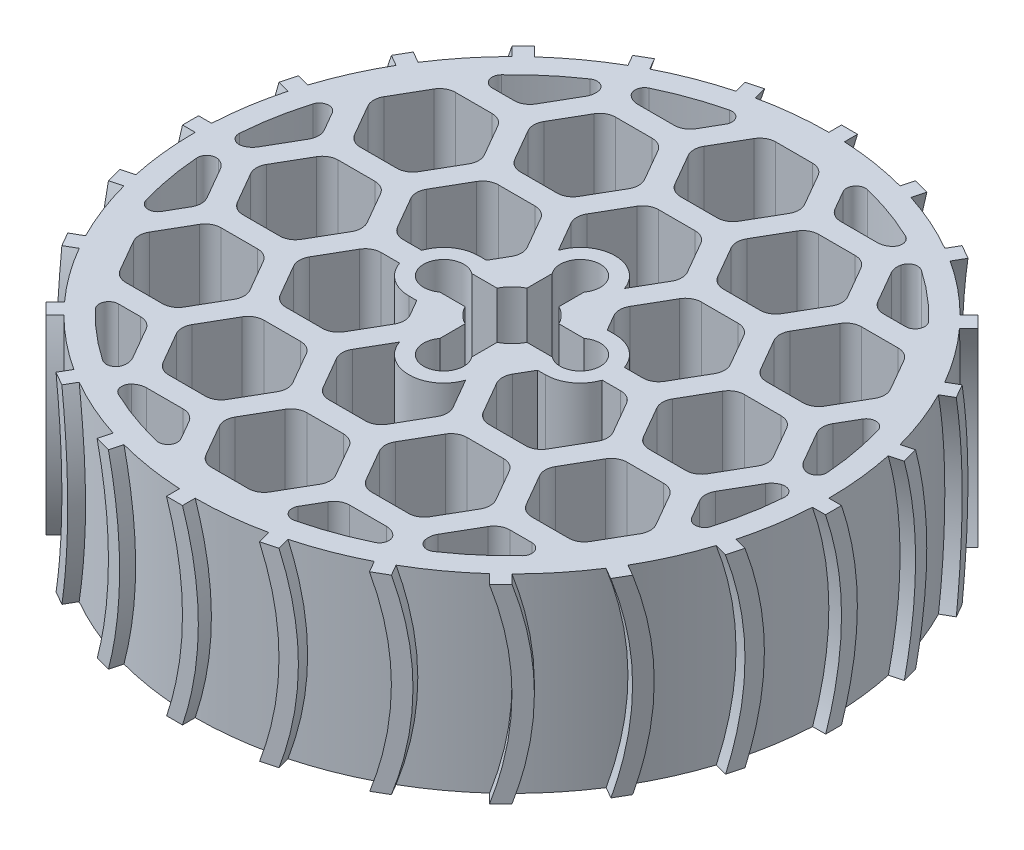
SolidWorks part; units mm, degrees
ref_plane "Front Plane" through (0, 0, 0) normal (0, 0, 1) x (1, 0, 0)
ref_plane "Top Plane" through (0, 0, 0) normal (0, 1, 0) x (1, 0, 0)
ref_plane "Right Plane" through (0, 0, 0) normal (1, 0, 0) x (0, 0, -1)
sketch "Sketch2" plane through (0, 0, 0) normal (0, 1, 0) x (1, 0, 0)
  line L0 (-17.7275, -5.0583) -> (-9.768, -5.0583)
  line L1 (-17.7275, 5.0583) -> (-9.768, 5.0583)
  line L2 (-21.548, 11) -> (-11, 11)
  line L3 (-21.548, -11) -> (-11, -11)
  line L4 (-21.548, 0) -> (0, 0) construction
  line L5 (11, 21.548) -> (11, 11)
  line L6 (-11, 21.548) -> (-11, 11)
  line L7 (5.0583, 17.7275) -> (5.0583, 9.768)
  line L8 (-5.0583, 17.7275) -> (-5.0583, 9.768)
  line L9 (21.548, -11) -> (11, -11)
  line L10 (21.548, 11) -> (11, 11)
  line L11 (17.7275, -5.0583) -> (9.768, -5.0583)
  line L12 (17.7275, 5.0583) -> (9.768, 5.0583)
  line L13 (-11, -21.548) -> (-11, -11)
  line L14 (11, -21.548) -> (11, -11)
  line L15 (-5.0583, -17.7275) -> (-5.0583, -9.768)
  line L16 (5.0583, -17.7275) -> (5.0583, -9.768)
  line L17 (0, 0) -> (-12.9904, 7.5) construction
  line L18 (-15.8771, -2.5) -> (-10.1036, -12.5)
  line L19 (-5.7735, -15) -> (5.7735, -15)
  line L20 (10.1036, -12.5) -> (15.8771, -2.5)
  line L21 (15.8771, 2.5) -> (10.1036, 12.5)
  line L22 (5.7735, 15) -> (-5.7735, 15)
  line L23 (-10.1036, 12.5) -> (-15.8771, 2.5)
  arc A0 (-21.548, 11) -> (-21.548, -11) centre (-21.548, 0) ccw
  arc A1 (-5.0583, 9.768) -> (-9.768, 5.0583) centre (0, 0) ccw
  circle A2 centre (-21.548, 0) radius 3.302
  circle A3 centre (-21.548, 0) radius 6.339
  arc A4 (-5.0583, 9.768) -> (-9.768, 5.0583) centre (0, 0) ccw
  arc A5 (11, 21.548) -> (-11, 21.548) centre (0, 21.548) ccw
  circle A6 centre (0, 21.548) radius 6.339
  circle A7 centre (0, 21.548) radius 3.302
  arc A8 (21.548, -11) -> (21.548, 11) centre (21.548, 0) ccw
  circle A9 centre (21.548, 0) radius 6.339
  circle A10 centre (21.548, 0) radius 3.302
  arc A11 (-11, -21.548) -> (11, -21.548) centre (0, -21.548) ccw
  circle A12 centre (0, -21.548) radius 6.339
  circle A13 centre (0, -21.548) radius 3.302
  arc A14 (9.768, 5.0583) -> (5.0583, 9.768) centre (0, 0) ccw
  arc A15 (5.0583, -9.768) -> (9.768, -5.0583) centre (0, 0) ccw
  arc A16 (-9.768, -5.0583) -> (-5.0583, -9.768) centre (0, 0) ccw
  circle A17 centre (0, 0) radius 100
  circle A18 centre (0, 0) radius 15 construction
  arc A19 (10.1036, 12.5) -> (5.7735, 15) centre (5.7735, 10) ccw
  arc A20 (15.8771, -2.5) -> (15.8771, 2.5) centre (11.547, 0) ccw
  arc A21 (10.1036, -12.5) -> (5.7735, -15) centre (5.7735, -10) cw
  arc A22 (-10.1036, -12.5) -> (-5.7735, -15) centre (-5.7735, -10) ccw
  arc A23 (-15.8771, -2.5) -> (-15.8771, 2.5) centre (-11.547, 0) cw
  arc A24 (-10.1036, 12.5) -> (-5.7735, 15) centre (-5.7735, 10) cw
  point P59 (0, 0)
  dimension "D1" = 6.604
  dimension "D2" = 12.678
  dimension "D3" = 11
  dimension "D8" = 22
  dimension "D10" = 200
  dimension "D12" = 5
  dimension "D4" = 21.548
  dimension "D5" = 7.9595
  dimension "D6" = 10.548
  dimension "D7" = 10.548
  dimension "D11" = 30
  dimension "D13" = 30
  dimension "D9" = 4
sketch "Sketch3" plane through (0, 0, 0) normal (0, 1, 0) x (1, 0, 0)
  line L0 (0, 0) -> (16.547, 0) construction
  line L1 (5.7735, 15) -> (-5.7735, 15)
  line L2 (-10.1036, 12.5) -> (-15.8771, 2.5)
  line L3 (-15.8771, -2.5) -> (-10.1036, -12.5)
  line L4 (-5.7735, -15) -> (5.7735, -15)
  line L5 (10.1036, -12.5) -> (15.8771, -2.5)
  line L6 (15.8771, 2.5) -> (10.1036, 12.5)
  line L7 (37.8164, 33.5) -> (26.2694, 33.5)
  line L8 (21.9393, 31) -> (16.1658, 21)
  line L9 (16.1658, 16) -> (21.9393, 6)
  line L10 (26.2694, 3.5) -> (37.8164, 3.5)
  line L11 (42.1466, 6) -> (47.9201, 16)
  line L12 (47.9201, 21) -> (42.1466, 31)
  line L13 (69.8594, 52) -> (58.3124, 52)
  line L14 (53.9823, 49.5) -> (48.2087, 39.5)
  line L15 (48.2087, 34.5) -> (53.9823, 24.5)
  line L16 (58.3124, 22) -> (69.8594, 22)
  line L17 (74.1895, 24.5) -> (79.963, 34.5)
  line L18 (79.963, 39.5) -> (74.1895, 49.5)
  line L19 (101.9023, 70.5) -> (90.3553, 70.5)
  line L20 (86.0252, 68) -> (80.2517, 58)
  line L21 (80.2517, 53) -> (86.0252, 43)
  line L22 (90.3553, 40.5) -> (101.9023, 40.5)
  line L23 (106.2324, 43) -> (112.006, 53)
  line L24 (112.006, 58) -> (106.2324, 68)
  line L25 (37.8164, 70.5) -> (26.2694, 70.5)
  line L26 (21.9393, 68) -> (16.1658, 58)
  line L27 (16.1658, 53) -> (21.9393, 43)
  line L28 (26.2694, 40.5) -> (37.8164, 40.5)
  line L29 (42.1466, 43) -> (47.9201, 53)
  line L30 (47.9201, 58) -> (42.1466, 68)
  line L31 (69.8594, 89) -> (58.3124, 89)
  line L32 (53.9823, 86.5) -> (48.2087, 76.5)
  line L33 (48.2087, 71.5) -> (53.9823, 61.5)
  line L34 (58.3124, 59) -> (69.8594, 59)
  line L35 (74.1895, 61.5) -> (79.963, 71.5)
  line L36 (79.963, 76.5) -> (74.1895, 86.5)
  line L37 (101.9023, 107.5) -> (90.3553, 107.5) [skipped]
  line L38 (86.0252, 105) -> (80.2517, 95) [skipped]
  line L39 (80.2517, 90) -> (86.0252, 80) [skipped]
  line L40 (90.3553, 77.5) -> (101.9023, 77.5) [skipped]
  line L41 (106.2324, 80) -> (112.006, 90) [skipped]
  line L42 (112.006, 95) -> (106.2324, 105) [skipped]
  line L43 (37.8164, 107.5) -> (26.2694, 107.5)
  line L44 (21.9393, 105) -> (16.1658, 95)
  line L45 (16.1658, 90) -> (21.9393, 80)
  line L46 (26.2694, 77.5) -> (37.8164, 77.5)
  line L47 (42.1466, 80) -> (47.9201, 90)
  line L48 (47.9201, 95) -> (42.1466, 105)
  line L49 (69.8594, 126) -> (58.3124, 126) [skipped]
  line L50 (53.9823, 123.5) -> (48.2087, 113.5) [skipped]
  line L51 (48.2087, 108.5) -> (53.9823, 98.5) [skipped]
  line L52 (58.3124, 96) -> (69.8594, 96) [skipped]
  line L53 (74.1895, 98.5) -> (79.963, 108.5) [skipped]
  line L54 (79.963, 113.5) -> (74.1895, 123.5) [skipped]
  line L55 (101.9023, 144.5) -> (90.3553, 144.5) [skipped]
  line L56 (86.0252, 142) -> (80.2517, 132) [skipped]
  line L57 (80.2517, 127) -> (86.0252, 117) [skipped]
  line L58 (90.3553, 114.5) -> (101.9023, 114.5) [skipped]
  line L59 (106.2324, 117) -> (112.006, 127) [skipped]
  line L60 (112.006, 132) -> (106.2324, 142) [skipped]
  line L61 (37.8164, 144.5) -> (26.2694, 144.5) [skipped]
  line L62 (21.9393, 142) -> (16.1658, 132) [skipped]
  line L63 (16.1658, 127) -> (21.9393, 117) [skipped]
  line L64 (26.2694, 114.5) -> (37.8164, 114.5) [skipped]
  line L65 (42.1466, 117) -> (47.9201, 127) [skipped]
  line L66 (47.9201, 132) -> (42.1466, 142) [skipped]
  line L67 (69.8594, 163) -> (58.3124, 163) [skipped]
  line L68 (53.9823, 160.5) -> (48.2087, 150.5) [skipped]
  line L69 (48.2087, 145.5) -> (53.9823, 135.5) [skipped]
  line L70 (58.3124, 133) -> (69.8594, 133) [skipped]
  line L71 (74.1895, 135.5) -> (79.963, 145.5) [skipped]
  line L72 (79.963, 150.5) -> (74.1895, 160.5) [skipped]
  line L73 (101.9023, 181.5) -> (90.3553, 181.5) [skipped]
  line L74 (86.0252, 179) -> (80.2517, 169) [skipped]
  line L75 (80.2517, 164) -> (86.0252, 154) [skipped]
  line L76 (90.3553, 151.5) -> (101.9023, 151.5) [skipped]
  line L77 (106.2324, 154) -> (112.006, 164) [skipped]
  line L78 (112.006, 169) -> (106.2324, 179) [skipped]
  line L79 (5.7735, 52) -> (-5.7735, 52) [skipped]
  line L80 (-10.1036, 49.5) -> (-15.8771, 39.5) [skipped]
  line L81 (-15.8771, 34.5) -> (-10.1036, 24.5) [skipped]
  line L82 (-5.7735, 22) -> (5.7735, 22) [skipped]
  line L83 (10.1036, 24.5) -> (15.8771, 34.5) [skipped]
  line L84 (15.8771, 39.5) -> (10.1036, 49.5) [skipped]
  line L85 (5.7735, 89) -> (-5.7735, 89) [skipped]
  line L86 (-10.1036, 86.5) -> (-15.8771, 76.5) [skipped]
  line L87 (-15.8771, 71.5) -> (-10.1036, 61.5) [skipped]
  line L88 (-5.7735, 59) -> (5.7735, 59) [skipped]
  line L89 (10.1036, 61.5) -> (15.8771, 71.5) [skipped]
  line L90 (15.8771, 76.5) -> (10.1036, 86.5) [skipped]
  line L91 (5.7735, 126) -> (-5.7735, 126) [skipped]
  line L92 (-10.1036, 123.5) -> (-15.8771, 113.5) [skipped]
  line L93 (-15.8771, 108.5) -> (-10.1036, 98.5) [skipped]
  line L94 (-5.7735, 96) -> (5.7735, 96) [skipped]
  line L95 (10.1036, 98.5) -> (15.8771, 108.5) [skipped]
  line L96 (15.8771, 113.5) -> (10.1036, 123.5) [skipped]
  line L97 (0, 0) -> (83.1384, 48) construction
  line L98 (112.006, 21) -> (106.2324, 31)
  line L99 (101.9023, 33.5) -> (90.3553, 33.5)
  line L100 (86.0252, 31) -> (80.2517, 21)
  line L101 (80.2517, 16) -> (86.0252, 6)
  line L102 (90.3553, 3.5) -> (101.9023, 3.5)
  line L103 (106.2324, 6) -> (112.006, 16)
  line L104 (112.006, -16) -> (106.2324, -6)
  line L105 (101.9023, -3.5) -> (90.3553, -3.5)
  line L106 (86.0252, -6) -> (80.2517, -16)
  line L107 (80.2517, -21) -> (86.0252, -31)
  line L108 (90.3553, -33.5) -> (101.9023, -33.5)
  line L109 (106.2324, -31) -> (112.006, -21)
  line L110 (112.006, -53) -> (106.2324, -43)
  line L111 (101.9023, -40.5) -> (90.3553, -40.5)
  line L112 (86.0252, -43) -> (80.2517, -53)
  line L113 (80.2517, -58) -> (86.0252, -68)
  line L114 (90.3553, -70.5) -> (101.9023, -70.5)
  line L115 (106.2324, -68) -> (112.006, -58)
  line L116 (79.963, -34.5) -> (74.1895, -24.5)
  line L117 (69.8594, -22) -> (58.3124, -22)
  line L118 (53.9823, -24.5) -> (48.2087, -34.5)
  line L119 (48.2087, -39.5) -> (53.9823, -49.5)
  line L120 (58.3124, -52) -> (69.8594, -52)
  line L121 (74.1895, -49.5) -> (79.963, -39.5)
  line L122 (79.963, 2.5) -> (74.1895, 12.5)
  line L123 (69.8594, 15) -> (58.3124, 15)
  line L124 (53.9823, 12.5) -> (48.2087, 2.5)
  line L125 (48.2087, -2.5) -> (53.9823, -12.5)
  line L126 (58.3124, -15) -> (69.8594, -15)
  line L127 (74.1895, -12.5) -> (79.963, -2.5)
  line L128 (47.9201, -16) -> (42.1466, -6)
  line L129 (37.8164, -3.5) -> (26.2694, -3.5)
  line L130 (21.9393, -6) -> (16.1658, -16)
  line L131 (16.1658, -21) -> (21.9393, -31)
  line L132 (26.2694, -33.5) -> (37.8164, -33.5)
  line L133 (42.1466, -31) -> (47.9201, -21)
  line L134 (74.1895, -86.5) -> (79.963, -76.5)
  line L135 (79.963, -71.5) -> (74.1895, -61.5)
  line L136 (69.8594, -59) -> (58.3124, -59)
  line L137 (53.9823, -61.5) -> (48.2087, -71.5)
  line L138 (48.2087, -76.5) -> (53.9823, -86.5)
  line L139 (58.3124, -89) -> (69.8594, -89)
  line L140 (42.1466, -105) -> (47.9201, -95)
  line L141 (47.9201, -90) -> (42.1466, -80)
  line L142 (37.8164, -77.5) -> (26.2694, -77.5)
  line L143 (21.9393, -80) -> (16.1658, -90)
  line L144 (16.1658, -95) -> (21.9393, -105)
  line L145 (26.2694, -107.5) -> (37.8164, -107.5)
  line L146 (10.1036, -123.5) -> (15.8771, -113.5)
  line L147 (15.8771, -108.5) -> (10.1036, -98.5)
  line L148 (5.7735, -96) -> (-5.7735, -96)
  line L149 (-10.1036, -98.5) -> (-15.8771, -108.5)
  line L150 (-15.8771, -113.5) -> (-10.1036, -123.5)
  line L151 (-5.7735, -126) -> (5.7735, -126)
  line L152 (10.1036, -86.5) -> (15.8771, -76.5)
  line L153 (15.8771, -71.5) -> (10.1036, -61.5)
  line L154 (5.7735, -59) -> (-5.7735, -59)
  line L155 (-10.1036, -61.5) -> (-15.8771, -71.5)
  line L156 (-15.8771, -76.5) -> (-10.1036, -86.5)
  line L157 (-5.7735, -89) -> (5.7735, -89)
  line L158 (42.1466, -68) -> (47.9201, -58)
  line L159 (47.9201, -53) -> (42.1466, -43)
  line L160 (37.8164, -40.5) -> (26.2694, -40.5)
  line L161 (21.9393, -43) -> (16.1658, -53)
  line L162 (16.1658, -58) -> (21.9393, -68)
  line L163 (26.2694, -70.5) -> (37.8164, -70.5)
  line L164 (10.1036, -49.5) -> (15.8771, -39.5)
  line L165 (15.8771, -34.5) -> (10.1036, -24.5)
  line L166 (5.7735, -22) -> (-5.7735, -22)
  line L167 (-10.1036, -24.5) -> (-15.8771, -34.5)
  line L168 (-15.8771, -39.5) -> (-10.1036, -49.5)
  line L169 (-5.7735, -52) -> (5.7735, -52)
  line L170 (-37.8164, -107.5) -> (-26.2694, -107.5)
  line L171 (-21.9393, -105) -> (-16.1658, -95)
  line L172 (-16.1658, -90) -> (-21.9393, -80)
  line L173 (-26.2694, -77.5) -> (-37.8164, -77.5)
  line L174 (-42.1466, -80) -> (-47.9201, -90)
  line L175 (-47.9201, -95) -> (-42.1466, -105)
  line L176 (-69.8594, -89) -> (-58.3124, -89)
  line L177 (-53.9823, -86.5) -> (-48.2087, -76.5)
  line L178 (-48.2087, -71.5) -> (-53.9823, -61.5)
  line L179 (-58.3124, -59) -> (-69.8594, -59)
  line L180 (-74.1895, -61.5) -> (-79.963, -71.5)
  line L181 (-79.963, -76.5) -> (-74.1895, -86.5)
  line L182 (-101.9023, -70.5) -> (-90.3553, -70.5)
  line L183 (-86.0252, -68) -> (-80.2517, -58)
  line L184 (-80.2517, -53) -> (-86.0252, -43)
  line L185 (-90.3553, -40.5) -> (-101.9023, -40.5)
  line L186 (-106.2324, -43) -> (-112.006, -53)
  line L187 (-112.006, -58) -> (-106.2324, -68)
  line L188 (-69.8594, -52) -> (-58.3124, -52)
  line L189 (-53.9823, -49.5) -> (-48.2087, -39.5)
  line L190 (-48.2087, -34.5) -> (-53.9823, -24.5)
  line L191 (-58.3124, -22) -> (-69.8594, -22)
  line L192 (-74.1895, -24.5) -> (-79.963, -34.5)
  line L193 (-79.963, -39.5) -> (-74.1895, -49.5)
  line L194 (-37.8164, -70.5) -> (-26.2694, -70.5)
  line L195 (-21.9393, -68) -> (-16.1658, -58)
  line L196 (-16.1658, -53) -> (-21.9393, -43)
  line L197 (-26.2694, -40.5) -> (-37.8164, -40.5)
  line L198 (-42.1466, -43) -> (-47.9201, -53)
  line L199 (-47.9201, -58) -> (-42.1466, -68)
  line L200 (-37.8164, -33.5) -> (-26.2694, -33.5)
  line L201 (-21.9393, -31) -> (-16.1658, -21)
  line L202 (-16.1658, -16) -> (-21.9393, -6)
  line L203 (-26.2694, -3.5) -> (-37.8164, -3.5)
  line L204 (-42.1466, -6) -> (-47.9201, -16)
  line L205 (-47.9201, -21) -> (-42.1466, -31)
  line L206 (-112.006, -21) -> (-106.2324, -31)
  line L207 (-101.9023, -33.5) -> (-90.3553, -33.5)
  line L208 (-86.0252, -31) -> (-80.2517, -21)
  line L209 (-80.2517, -16) -> (-86.0252, -6)
  line L210 (-90.3553, -3.5) -> (-101.9023, -3.5)
  line L211 (-106.2324, -6) -> (-112.006, -16)
  line L212 (-112.006, 16) -> (-106.2324, 6)
  line L213 (-101.9023, 3.5) -> (-90.3553, 3.5)
  line L214 (-86.0252, 6) -> (-80.2517, 16)
  line L215 (-80.2517, 21) -> (-86.0252, 31)
  line L216 (-90.3553, 33.5) -> (-101.9023, 33.5)
  line L217 (-106.2324, 31) -> (-112.006, 21)
  line L218 (-112.006, 53) -> (-106.2324, 43)
  line L219 (-101.9023, 40.5) -> (-90.3553, 40.5)
  line L220 (-86.0252, 43) -> (-80.2517, 53)
  line L221 (-80.2517, 58) -> (-86.0252, 68)
  line L222 (-90.3553, 70.5) -> (-101.9023, 70.5)
  line L223 (-106.2324, 68) -> (-112.006, 58)
  line L224 (-79.963, 34.5) -> (-74.1895, 24.5)
  line L225 (-69.8594, 22) -> (-58.3124, 22)
  line L226 (-53.9823, 24.5) -> (-48.2087, 34.5)
  line L227 (-48.2087, 39.5) -> (-53.9823, 49.5)
  line L228 (-58.3124, 52) -> (-69.8594, 52)
  line L229 (-74.1895, 49.5) -> (-79.963, 39.5)
  line L230 (-79.963, -2.5) -> (-74.1895, -12.5)
  line L231 (-69.8594, -15) -> (-58.3124, -15)
  line L232 (-53.9823, -12.5) -> (-48.2087, -2.5)
  line L233 (-48.2087, 2.5) -> (-53.9823, 12.5)
  line L234 (-58.3124, 15) -> (-69.8594, 15)
  line L235 (-74.1895, 12.5) -> (-79.963, 2.5)
  line L236 (-47.9201, 16) -> (-42.1466, 6)
  line L237 (-37.8164, 3.5) -> (-26.2694, 3.5)
  line L238 (-21.9393, 6) -> (-16.1658, 16)
  line L239 (-16.1658, 21) -> (-21.9393, 31)
  line L240 (-26.2694, 33.5) -> (-37.8164, 33.5)
  line L241 (-42.1466, 31) -> (-47.9201, 21)
  line L242 (-74.1895, 86.5) -> (-79.963, 76.5)
  line L243 (-79.963, 71.5) -> (-74.1895, 61.5)
  line L244 (-69.8594, 59) -> (-58.3124, 59)
  line L245 (-53.9823, 61.5) -> (-48.2087, 71.5)
  line L246 (-48.2087, 76.5) -> (-53.9823, 86.5)
  line L247 (-58.3124, 89) -> (-69.8594, 89)
  line L248 (-42.1466, 105) -> (-47.9201, 95)
  line L249 (-47.9201, 90) -> (-42.1466, 80)
  line L250 (-37.8164, 77.5) -> (-26.2694, 77.5)
  line L251 (-21.9393, 80) -> (-16.1658, 90)
  line L252 (-16.1658, 95) -> (-21.9393, 105)
  line L253 (-26.2694, 107.5) -> (-37.8164, 107.5)
  line L254 (-10.1036, 123.5) -> (-15.8771, 113.5)
  line L255 (-15.8771, 108.5) -> (-10.1036, 98.5)
  line L256 (-5.7735, 96) -> (5.7735, 96)
  line L257 (10.1036, 98.5) -> (15.8771, 108.5)
  line L258 (15.8771, 113.5) -> (10.1036, 123.5)
  line L259 (5.7735, 126) -> (-5.7735, 126)
  line L260 (-10.1036, 86.5) -> (-15.8771, 76.5)
  line L261 (-15.8771, 71.5) -> (-10.1036, 61.5)
  line L262 (-5.7735, 59) -> (5.7735, 59)
  line L263 (10.1036, 61.5) -> (15.8771, 71.5)
  line L264 (15.8771, 76.5) -> (10.1036, 86.5)
  line L265 (5.7735, 89) -> (-5.7735, 89)
  line L266 (-42.1466, 68) -> (-47.9201, 58)
  line L267 (-47.9201, 53) -> (-42.1466, 43)
  line L268 (-37.8164, 40.5) -> (-26.2694, 40.5)
  line L269 (-21.9393, 43) -> (-16.1658, 53)
  line L270 (-16.1658, 58) -> (-21.9393, 68)
  line L271 (-26.2694, 70.5) -> (-37.8164, 70.5)
  line L272 (-10.1036, 49.5) -> (-15.8771, 39.5)
  line L273 (-15.8771, 34.5) -> (-10.1036, 24.5)
  line L274 (-5.7735, 22) -> (5.7735, 22)
  line L275 (10.1036, 24.5) -> (15.8771, 34.5)
  line L276 (15.8771, 39.5) -> (10.1036, 49.5)
  line L277 (5.7735, 52) -> (-5.7735, 52)
  line L278 (0, 0) -> (0, 96) construction
  line L279 (0, 0) -> (-83.1384, 48) construction
  line L280 (-17.7275, -5.0583) -> (-9.768, -5.0583)
  line L281 (-17.7275, 5.0583) -> (-9.768, 5.0583)
  line L282 (-21.548, 11) -> (-11, 11)
  line L283 (-21.548, -11) -> (-11, -11)
  line L284 (0, 0) -> (-21.548, 0) construction
  line L285 (11, 21.548) -> (11, 11)
  line L286 (-11, 21.548) -> (-11, 11)
  line L287 (-5.0583, 17.7275) -> (-5.0583, 9.768)
  line L288 (5.0583, 17.7275) -> (5.0583, 9.768)
  line L289 (21.548, -11) -> (11, -11)
  line L290 (21.548, 11) -> (11, 11)
  line L291 (17.7275, 5.0583) -> (9.768, 5.0583)
  line L292 (17.7275, -5.0583) -> (9.768, -5.0583)
  line L293 (-11, -21.548) -> (-11, -11)
  line L294 (11, -21.548) -> (11, -11)
  line L295 (5.0583, -17.7275) -> (5.0583, -9.768)
  line L296 (-5.0583, -17.7275) -> (-5.0583, -9.768)
  line L297 (0, 0) -> (0, 21.548) construction
  circle A0 centre (0, 0) radius 15 construction
  arc A1 (10.1036, 12.5) -> (5.7735, 15) centre (5.7735, 10) ccw
  arc A2 (15.8771, 2.5) -> (15.8771, -2.5) centre (11.547, 0) cw
  arc A3 (5.7735, -15) -> (10.1036, -12.5) centre (5.7735, -10) ccw
  arc A4 (-5.7735, -15) -> (-10.1036, -12.5) centre (-5.7735, -10) cw
  arc A5 (-15.8771, -2.5) -> (-15.8771, 2.5) centre (-11.547, 0) cw
  arc A6 (-10.1036, 12.5) -> (-5.7735, 15) centre (-5.7735, 10) cw
  circle A7 centre (0, 0) radius 100
  arc A8 (21.9393, 31) -> (26.2694, 33.5) centre (26.2694, 28.5) cw
  arc A9 (42.1466, 31) -> (37.8164, 33.5) centre (37.8164, 28.5) ccw
  arc A10 (16.1658, 16) -> (16.1658, 21) centre (20.4959, 18.5) cw
  arc A11 (26.2694, 3.5) -> (21.9393, 6) centre (26.2694, 8.5) cw
  arc A12 (37.8164, 3.5) -> (42.1466, 6) centre (37.8164, 8.5) ccw
  arc A13 (47.9201, 21) -> (47.9201, 16) centre (43.5899, 18.5) cw
  arc A14 (53.9823, 49.5) -> (58.3124, 52) centre (58.3124, 47) cw
  arc A15 (74.1895, 49.5) -> (69.8594, 52) centre (69.8594, 47) ccw
  arc A16 (48.2087, 34.5) -> (48.2087, 39.5) centre (52.5389, 37) cw
  arc A17 (58.3124, 22) -> (53.9823, 24.5) centre (58.3124, 27) cw
  arc A18 (69.8594, 22) -> (74.1895, 24.5) centre (69.8594, 27) ccw
  arc A19 (79.963, 39.5) -> (79.963, 34.5) centre (75.6329, 37) cw
  arc A20 (86.0252, 68) -> (90.3553, 70.5) centre (90.3553, 65.5) cw
  arc A21 (106.2324, 68) -> (101.9023, 70.5) centre (101.9023, 65.5) ccw
  arc A22 (80.2517, 53) -> (80.2517, 58) centre (84.5818, 55.5) cw
  arc A23 (90.3553, 40.5) -> (86.0252, 43) centre (90.3553, 45.5) cw
  arc A24 (101.9023, 40.5) -> (106.2324, 43) centre (101.9023, 45.5) ccw
  arc A25 (112.006, 58) -> (112.006, 53) centre (107.6758, 55.5) cw
  arc A26 (21.9393, 68) -> (26.2694, 70.5) centre (26.2694, 65.5) cw
  arc A27 (42.1466, 68) -> (37.8164, 70.5) centre (37.8164, 65.5) ccw
  arc A28 (16.1658, 53) -> (16.1658, 58) centre (20.4959, 55.5) cw
  arc A29 (26.2694, 40.5) -> (21.9393, 43) centre (26.2694, 45.5) cw
  arc A30 (37.8164, 40.5) -> (42.1466, 43) centre (37.8164, 45.5) ccw
  arc A31 (47.9201, 58) -> (47.9201, 53) centre (43.5899, 55.5) cw
  arc A32 (53.9823, 86.5) -> (58.3124, 89) centre (58.3124, 84) cw
  arc A33 (74.1895, 86.5) -> (69.8594, 89) centre (69.8594, 84) ccw
  arc A34 (48.2087, 71.5) -> (48.2087, 76.5) centre (52.5389, 74) cw
  arc A35 (58.3124, 59) -> (53.9823, 61.5) centre (58.3124, 64) cw
  arc A36 (69.8594, 59) -> (74.1895, 61.5) centre (69.8594, 64) ccw
  arc A37 (79.963, 76.5) -> (79.963, 71.5) centre (75.6329, 74) cw
  arc A38 (86.0252, 105) -> (90.3553, 107.5) centre (90.3553, 102.5) cw [skipped]
  arc A39 (106.2324, 105) -> (101.9023, 107.5) centre (101.9023, 102.5) ccw [skipped]
  arc A40 (80.2517, 90) -> (80.2517, 95) centre (84.5818, 92.5) cw [skipped]
  arc A41 (90.3553, 77.5) -> (86.0252, 80) centre (90.3553, 82.5) cw [skipped]
  arc A42 (101.9023, 77.5) -> (106.2324, 80) centre (101.9023, 82.5) ccw [skipped]
  arc A43 (112.006, 95) -> (112.006, 90) centre (107.6758, 92.5) cw [skipped]
  arc A44 (21.9393, 105) -> (26.2694, 107.5) centre (26.2694, 102.5) cw
  arc A45 (42.1466, 105) -> (37.8164, 107.5) centre (37.8164, 102.5) ccw
  arc A46 (16.1658, 90) -> (16.1658, 95) centre (20.4959, 92.5) cw
  arc A47 (26.2694, 77.5) -> (21.9393, 80) centre (26.2694, 82.5) cw
  arc A48 (37.8164, 77.5) -> (42.1466, 80) centre (37.8164, 82.5) ccw
  arc A49 (47.9201, 95) -> (47.9201, 90) centre (43.5899, 92.5) cw
  arc A50 (53.9823, 123.5) -> (58.3124, 126) centre (58.3124, 121) cw [skipped]
  arc A51 (74.1895, 123.5) -> (69.8594, 126) centre (69.8594, 121) ccw [skipped]
  arc A52 (48.2087, 108.5) -> (48.2087, 113.5) centre (52.5389, 111) cw [skipped]
  arc A53 (58.3124, 96) -> (53.9823, 98.5) centre (58.3124, 101) cw [skipped]
  arc A54 (69.8594, 96) -> (74.1895, 98.5) centre (69.8594, 101) ccw [skipped]
  arc A55 (79.963, 113.5) -> (79.963, 108.5) centre (75.6329, 111) cw [skipped]
  arc A56 (86.0252, 142) -> (90.3553, 144.5) centre (90.3553, 139.5) cw [skipped]
  arc A57 (106.2324, 142) -> (101.9023, 144.5) centre (101.9023, 139.5) ccw [skipped]
  arc A58 (80.2517, 127) -> (80.2517, 132) centre (84.5818, 129.5) cw [skipped]
  arc A59 (90.3553, 114.5) -> (86.0252, 117) centre (90.3553, 119.5) cw [skipped]
  arc A60 (101.9023, 114.5) -> (106.2324, 117) centre (101.9023, 119.5) ccw [skipped]
  arc A61 (112.006, 132) -> (112.006, 127) centre (107.6758, 129.5) cw [skipped]
  arc A62 (21.9393, 142) -> (26.2694, 144.5) centre (26.2694, 139.5) cw [skipped]
  arc A63 (42.1466, 142) -> (37.8164, 144.5) centre (37.8164, 139.5) ccw [skipped]
  arc A64 (16.1658, 127) -> (16.1658, 132) centre (20.4959, 129.5) cw [skipped]
  arc A65 (26.2694, 114.5) -> (21.9393, 117) centre (26.2694, 119.5) cw [skipped]
  arc A66 (37.8164, 114.5) -> (42.1466, 117) centre (37.8164, 119.5) ccw [skipped]
  arc A67 (47.9201, 132) -> (47.9201, 127) centre (43.5899, 129.5) cw [skipped]
  arc A68 (53.9823, 160.5) -> (58.3124, 163) centre (58.3124, 158) cw [skipped]
  arc A69 (74.1895, 160.5) -> (69.8594, 163) centre (69.8594, 158) ccw [skipped]
  arc A70 (48.2087, 145.5) -> (48.2087, 150.5) centre (52.5389, 148) cw [skipped]
  arc A71 (58.3124, 133) -> (53.9823, 135.5) centre (58.3124, 138) cw [skipped]
  arc A72 (69.8594, 133) -> (74.1895, 135.5) centre (69.8594, 138) ccw [skipped]
  arc A73 (79.963, 150.5) -> (79.963, 145.5) centre (75.6329, 148) cw [skipped]
  arc A74 (86.0252, 179) -> (90.3553, 181.5) centre (90.3553, 176.5) cw [skipped]
  arc A75 (106.2324, 179) -> (101.9023, 181.5) centre (101.9023, 176.5) ccw [skipped]
  arc A76 (80.2517, 164) -> (80.2517, 169) centre (84.5818, 166.5) cw [skipped]
  arc A77 (90.3553, 151.5) -> (86.0252, 154) centre (90.3553, 156.5) cw [skipped]
  arc A78 (101.9023, 151.5) -> (106.2324, 154) centre (101.9023, 156.5) ccw [skipped]
  arc A79 (112.006, 169) -> (112.006, 164) centre (107.6758, 166.5) cw [skipped]
  arc A80 (-10.1036, 49.5) -> (-5.7735, 52) centre (-5.7735, 47) cw [skipped]
  arc A81 (10.1036, 49.5) -> (5.7735, 52) centre (5.7735, 47) ccw [skipped]
  arc A82 (-15.8771, 34.5) -> (-15.8771, 39.5) centre (-11.547, 37) cw [skipped]
  arc A83 (-5.7735, 22) -> (-10.1036, 24.5) centre (-5.7735, 27) cw [skipped]
  arc A84 (5.7735, 22) -> (10.1036, 24.5) centre (5.7735, 27) ccw [skipped]
  arc A85 (15.8771, 39.5) -> (15.8771, 34.5) centre (11.547, 37) cw [skipped]
  arc A86 (-10.1036, 86.5) -> (-5.7735, 89) centre (-5.7735, 84) cw [skipped]
  arc A87 (10.1036, 86.5) -> (5.7735, 89) centre (5.7735, 84) ccw [skipped]
  arc A88 (-15.8771, 71.5) -> (-15.8771, 76.5) centre (-11.547, 74) cw [skipped]
  arc A89 (-5.7735, 59) -> (-10.1036, 61.5) centre (-5.7735, 64) cw [skipped]
  arc A90 (5.7735, 59) -> (10.1036, 61.5) centre (5.7735, 64) ccw [skipped]
  arc A91 (15.8771, 76.5) -> (15.8771, 71.5) centre (11.547, 74) cw [skipped]
  arc A92 (-10.1036, 123.5) -> (-5.7735, 126) centre (-5.7735, 121) cw [skipped]
  arc A93 (10.1036, 123.5) -> (5.7735, 126) centre (5.7735, 121) ccw [skipped]
  arc A94 (-15.8771, 108.5) -> (-15.8771, 113.5) centre (-11.547, 111) cw [skipped]
  arc A95 (-5.7735, 96) -> (-10.1036, 98.5) centre (-5.7735, 101) cw [skipped]
  arc A96 (5.7735, 96) -> (10.1036, 98.5) centre (5.7735, 101) ccw [skipped]
  arc A97 (15.8771, 113.5) -> (15.8771, 108.5) centre (11.547, 111) cw [skipped]
  arc A98 (101.9023, 33.5) -> (106.2324, 31) centre (101.9023, 28.5) cw
  arc A99 (86.0252, 31) -> (90.3553, 33.5) centre (90.3553, 28.5) cw
  arc A100 (80.2517, 16) -> (80.2517, 21) centre (84.5818, 18.5) cw
  arc A101 (86.0252, 6) -> (90.3553, 3.5) centre (90.3553, 8.5) ccw
  arc A102 (106.2324, 6) -> (101.9023, 3.5) centre (101.9023, 8.5) cw
  arc A103 (112.006, 16) -> (112.006, 21) centre (107.6758, 18.5) ccw
  arc A104 (101.9023, -3.5) -> (106.2324, -6) centre (101.9023, -8.5) cw
  arc A105 (86.0252, -6) -> (90.3553, -3.5) centre (90.3553, -8.5) cw
  arc A106 (80.2517, -21) -> (80.2517, -16) centre (84.5818, -18.5) cw
  arc A107 (86.0252, -31) -> (90.3553, -33.5) centre (90.3553, -28.5) ccw
  arc A108 (106.2324, -31) -> (101.9023, -33.5) centre (101.9023, -28.5) cw
  arc A109 (112.006, -21) -> (112.006, -16) centre (107.6758, -18.5) ccw
  arc A110 (101.9023, -40.5) -> (106.2324, -43) centre (101.9023, -45.5) cw
  arc A111 (86.0252, -43) -> (90.3553, -40.5) centre (90.3553, -45.5) cw
  arc A112 (80.2517, -58) -> (80.2517, -53) centre (84.5818, -55.5) cw
  arc A113 (86.0252, -68) -> (90.3553, -70.5) centre (90.3553, -65.5) ccw
  arc A114 (106.2324, -68) -> (101.9023, -70.5) centre (101.9023, -65.5) cw
  arc A115 (112.006, -58) -> (112.006, -53) centre (107.6758, -55.5) ccw
  arc A116 (69.8594, -22) -> (74.1895, -24.5) centre (69.8594, -27) cw
  arc A117 (53.9823, -24.5) -> (58.3124, -22) centre (58.3124, -27) cw
  arc A118 (48.2087, -39.5) -> (48.2087, -34.5) centre (52.5389, -37) cw
  arc A119 (53.9823, -49.5) -> (58.3124, -52) centre (58.3124, -47) ccw
  arc A120 (74.1895, -49.5) -> (69.8594, -52) centre (69.8594, -47) cw
  arc A121 (79.963, -39.5) -> (79.963, -34.5) centre (75.6329, -37) ccw
  arc A122 (69.8594, 15) -> (74.1895, 12.5) centre (69.8594, 10) cw
  arc A123 (53.9823, 12.5) -> (58.3124, 15) centre (58.3124, 10) cw
  arc A124 (48.2087, -2.5) -> (48.2087, 2.5) centre (52.5389, 0) cw
  arc A125 (53.9823, -12.5) -> (58.3124, -15) centre (58.3124, -10) ccw
  arc A126 (74.1895, -12.5) -> (69.8594, -15) centre (69.8594, -10) cw
  arc A127 (79.963, -2.5) -> (79.963, 2.5) centre (75.6329, 0) ccw
  arc A128 (37.8164, -3.5) -> (42.1466, -6) centre (37.8164, -8.5) cw
  arc A129 (21.9393, -6) -> (26.2694, -3.5) centre (26.2694, -8.5) cw
  arc A130 (16.1658, -21) -> (16.1658, -16) centre (20.4959, -18.5) cw
  arc A131 (21.9393, -31) -> (26.2694, -33.5) centre (26.2694, -28.5) ccw
  arc A132 (42.1466, -31) -> (37.8164, -33.5) centre (37.8164, -28.5) cw
  arc A133 (47.9201, -21) -> (47.9201, -16) centre (43.5899, -18.5) ccw
  arc A134 (79.963, -71.5) -> (79.963, -76.5) centre (75.6329, -74) cw
  arc A135 (69.8594, -59) -> (74.1895, -61.5) centre (69.8594, -64) cw
  arc A136 (53.9823, -61.5) -> (58.3124, -59) centre (58.3124, -64) cw
  arc A137 (48.2087, -71.5) -> (48.2087, -76.5) centre (52.5389, -74) ccw
  arc A138 (58.3124, -89) -> (53.9823, -86.5) centre (58.3124, -84) cw
  arc A139 (69.8594, -89) -> (74.1895, -86.5) centre (69.8594, -84) ccw
  arc A140 (47.9201, -90) -> (47.9201, -95) centre (43.5899, -92.5) cw
  arc A141 (37.8164, -77.5) -> (42.1466, -80) centre (37.8164, -82.5) cw
  arc A142 (21.9393, -80) -> (26.2694, -77.5) centre (26.2694, -82.5) cw
  arc A143 (16.1658, -90) -> (16.1658, -95) centre (20.4959, -92.5) ccw
  arc A144 (26.2694, -107.5) -> (21.9393, -105) centre (26.2694, -102.5) cw
  arc A145 (37.8164, -107.5) -> (42.1466, -105) centre (37.8164, -102.5) ccw
  arc A146 (15.8771, -108.5) -> (15.8771, -113.5) centre (11.547, -111) cw
  arc A147 (5.7735, -96) -> (10.1036, -98.5) centre (5.7735, -101) cw
  arc A148 (-10.1036, -98.5) -> (-5.7735, -96) centre (-5.7735, -101) cw
  arc A149 (-15.8771, -108.5) -> (-15.8771, -113.5) centre (-11.547, -111) ccw
  arc A150 (-5.7735, -126) -> (-10.1036, -123.5) centre (-5.7735, -121) cw
  arc A151 (5.7735, -126) -> (10.1036, -123.5) centre (5.7735, -121) ccw
  arc A152 (15.8771, -71.5) -> (15.8771, -76.5) centre (11.547, -74) cw
  arc A153 (5.7735, -59) -> (10.1036, -61.5) centre (5.7735, -64) cw
  arc A154 (-10.1036, -61.5) -> (-5.7735, -59) centre (-5.7735, -64) cw
  arc A155 (-15.8771, -71.5) -> (-15.8771, -76.5) centre (-11.547, -74) ccw
  arc A156 (-5.7735, -89) -> (-10.1036, -86.5) centre (-5.7735, -84) cw
  arc A157 (5.7735, -89) -> (10.1036, -86.5) centre (5.7735, -84) ccw
  arc A158 (47.9201, -53) -> (47.9201, -58) centre (43.5899, -55.5) cw
  arc A159 (37.8164, -40.5) -> (42.1466, -43) centre (37.8164, -45.5) cw
  arc A160 (21.9393, -43) -> (26.2694, -40.5) centre (26.2694, -45.5) cw
  arc A161 (16.1658, -53) -> (16.1658, -58) centre (20.4959, -55.5) ccw
  arc A162 (26.2694, -70.5) -> (21.9393, -68) centre (26.2694, -65.5) cw
  arc A163 (37.8164, -70.5) -> (42.1466, -68) centre (37.8164, -65.5) ccw
  arc A164 (15.8771, -34.5) -> (15.8771, -39.5) centre (11.547, -37) cw
  arc A165 (5.7735, -22) -> (10.1036, -24.5) centre (5.7735, -27) cw
  arc A166 (-10.1036, -24.5) -> (-5.7735, -22) centre (-5.7735, -27) cw
  arc A167 (-15.8771, -34.5) -> (-15.8771, -39.5) centre (-11.547, -37) ccw
  arc A168 (-5.7735, -52) -> (-10.1036, -49.5) centre (-5.7735, -47) cw
  arc A169 (5.7735, -52) -> (10.1036, -49.5) centre (5.7735, -47) ccw
  arc A170 (-21.9393, -105) -> (-26.2694, -107.5) centre (-26.2694, -102.5) cw
  arc A171 (-16.1658, -90) -> (-16.1658, -95) centre (-20.4959, -92.5) cw
  arc A172 (-26.2694, -77.5) -> (-21.9393, -80) centre (-26.2694, -82.5) cw
  arc A173 (-37.8164, -77.5) -> (-42.1466, -80) centre (-37.8164, -82.5) ccw
  arc A174 (-47.9201, -95) -> (-47.9201, -90) centre (-43.5899, -92.5) cw
  arc A175 (-42.1466, -105) -> (-37.8164, -107.5) centre (-37.8164, -102.5) ccw
  arc A176 (-53.9823, -86.5) -> (-58.3124, -89) centre (-58.3124, -84) cw
  arc A177 (-48.2087, -71.5) -> (-48.2087, -76.5) centre (-52.5389, -74) cw
  arc A178 (-58.3124, -59) -> (-53.9823, -61.5) centre (-58.3124, -64) cw
  arc A179 (-69.8594, -59) -> (-74.1895, -61.5) centre (-69.8594, -64) ccw
  arc A180 (-79.963, -76.5) -> (-79.963, -71.5) centre (-75.6329, -74) cw
  arc A181 (-74.1895, -86.5) -> (-69.8594, -89) centre (-69.8594, -84) ccw
  arc A182 (-86.0252, -68) -> (-90.3553, -70.5) centre (-90.3553, -65.5) cw
  arc A183 (-80.2517, -53) -> (-80.2517, -58) centre (-84.5818, -55.5) cw
  arc A184 (-90.3553, -40.5) -> (-86.0252, -43) centre (-90.3553, -45.5) cw
  arc A185 (-101.9023, -40.5) -> (-106.2324, -43) centre (-101.9023, -45.5) ccw
  arc A186 (-112.006, -58) -> (-112.006, -53) centre (-107.6758, -55.5) cw
  arc A187 (-106.2324, -68) -> (-101.9023, -70.5) centre (-101.9023, -65.5) ccw
  arc A188 (-53.9823, -49.5) -> (-58.3124, -52) centre (-58.3124, -47) cw
  arc A189 (-48.2087, -34.5) -> (-48.2087, -39.5) centre (-52.5389, -37) cw
  arc A190 (-58.3124, -22) -> (-53.9823, -24.5) centre (-58.3124, -27) cw
  arc A191 (-69.8594, -22) -> (-74.1895, -24.5) centre (-69.8594, -27) ccw
  arc A192 (-79.963, -39.5) -> (-79.963, -34.5) centre (-75.6329, -37) cw
  arc A193 (-74.1895, -49.5) -> (-69.8594, -52) centre (-69.8594, -47) ccw
  arc A194 (-21.9393, -68) -> (-26.2694, -70.5) centre (-26.2694, -65.5) cw
  arc A195 (-16.1658, -53) -> (-16.1658, -58) centre (-20.4959, -55.5) cw
  arc A196 (-26.2694, -40.5) -> (-21.9393, -43) centre (-26.2694, -45.5) cw
  arc A197 (-37.8164, -40.5) -> (-42.1466, -43) centre (-37.8164, -45.5) ccw
  arc A198 (-47.9201, -58) -> (-47.9201, -53) centre (-43.5899, -55.5) cw
  arc A199 (-42.1466, -68) -> (-37.8164, -70.5) centre (-37.8164, -65.5) ccw
  arc A200 (-21.9393, -31) -> (-26.2694, -33.5) centre (-26.2694, -28.5) cw
  arc A201 (-16.1658, -16) -> (-16.1658, -21) centre (-20.4959, -18.5) cw
  arc A202 (-26.2694, -3.5) -> (-21.9393, -6) centre (-26.2694, -8.5) cw
  arc A203 (-37.8164, -3.5) -> (-42.1466, -6) centre (-37.8164, -8.5) ccw
  arc A204 (-47.9201, -21) -> (-47.9201, -16) centre (-43.5899, -18.5) cw
  arc A205 (-42.1466, -31) -> (-37.8164, -33.5) centre (-37.8164, -28.5) ccw
  arc A206 (-101.9023, -33.5) -> (-106.2324, -31) centre (-101.9023, -28.5) cw
  arc A207 (-86.0252, -31) -> (-90.3553, -33.5) centre (-90.3553, -28.5) cw
  arc A208 (-80.2517, -16) -> (-80.2517, -21) centre (-84.5818, -18.5) cw
  arc A209 (-86.0252, -6) -> (-90.3553, -3.5) centre (-90.3553, -8.5) ccw
  arc A210 (-106.2324, -6) -> (-101.9023, -3.5) centre (-101.9023, -8.5) cw
  arc A211 (-112.006, -16) -> (-112.006, -21) centre (-107.6758, -18.5) ccw
  arc A212 (-101.9023, 3.5) -> (-106.2324, 6) centre (-101.9023, 8.5) cw
  arc A213 (-86.0252, 6) -> (-90.3553, 3.5) centre (-90.3553, 8.5) cw
  arc A214 (-80.2517, 21) -> (-80.2517, 16) centre (-84.5818, 18.5) cw
  arc A215 (-86.0252, 31) -> (-90.3553, 33.5) centre (-90.3553, 28.5) ccw
  arc A216 (-106.2324, 31) -> (-101.9023, 33.5) centre (-101.9023, 28.5) cw
  arc A217 (-112.006, 21) -> (-112.006, 16) centre (-107.6758, 18.5) ccw
  arc A218 (-101.9023, 40.5) -> (-106.2324, 43) centre (-101.9023, 45.5) cw
  arc A219 (-86.0252, 43) -> (-90.3553, 40.5) centre (-90.3553, 45.5) cw
  arc A220 (-80.2517, 58) -> (-80.2517, 53) centre (-84.5818, 55.5) cw
  arc A221 (-86.0252, 68) -> (-90.3553, 70.5) centre (-90.3553, 65.5) ccw
  arc A222 (-106.2324, 68) -> (-101.9023, 70.5) centre (-101.9023, 65.5) cw
  arc A223 (-112.006, 58) -> (-112.006, 53) centre (-107.6758, 55.5) ccw
  arc A224 (-69.8594, 22) -> (-74.1895, 24.5) centre (-69.8594, 27) cw
  arc A225 (-53.9823, 24.5) -> (-58.3124, 22) centre (-58.3124, 27) cw
  arc A226 (-48.2087, 39.5) -> (-48.2087, 34.5) centre (-52.5389, 37) cw
  arc A227 (-53.9823, 49.5) -> (-58.3124, 52) centre (-58.3124, 47) ccw
  arc A228 (-74.1895, 49.5) -> (-69.8594, 52) centre (-69.8594, 47) cw
  arc A229 (-79.963, 39.5) -> (-79.963, 34.5) centre (-75.6329, 37) ccw
  arc A230 (-69.8594, -15) -> (-74.1895, -12.5) centre (-69.8594, -10) cw
  arc A231 (-53.9823, -12.5) -> (-58.3124, -15) centre (-58.3124, -10) cw
  arc A232 (-48.2087, 2.5) -> (-48.2087, -2.5) centre (-52.5389, 0) cw
  arc A233 (-53.9823, 12.5) -> (-58.3124, 15) centre (-58.3124, 10) ccw
  arc A234 (-74.1895, 12.5) -> (-69.8594, 15) centre (-69.8594, 10) cw
  arc A235 (-79.963, 2.5) -> (-79.963, -2.5) centre (-75.6329, 0) ccw
  arc A236 (-37.8164, 3.5) -> (-42.1466, 6) centre (-37.8164, 8.5) cw
  arc A237 (-21.9393, 6) -> (-26.2694, 3.5) centre (-26.2694, 8.5) cw
  arc A238 (-16.1658, 21) -> (-16.1658, 16) centre (-20.4959, 18.5) cw
  arc A239 (-21.9393, 31) -> (-26.2694, 33.5) centre (-26.2694, 28.5) ccw
  arc A240 (-42.1466, 31) -> (-37.8164, 33.5) centre (-37.8164, 28.5) cw
  arc A241 (-47.9201, 21) -> (-47.9201, 16) centre (-43.5899, 18.5) ccw
  arc A242 (-79.963, 71.5) -> (-79.963, 76.5) centre (-75.6329, 74) cw
  arc A243 (-69.8594, 59) -> (-74.1895, 61.5) centre (-69.8594, 64) cw
  arc A244 (-53.9823, 61.5) -> (-58.3124, 59) centre (-58.3124, 64) cw
  arc A245 (-48.2087, 71.5) -> (-48.2087, 76.5) centre (-52.5389, 74) ccw
  arc A246 (-58.3124, 89) -> (-53.9823, 86.5) centre (-58.3124, 84) cw
  arc A247 (-69.8594, 89) -> (-74.1895, 86.5) centre (-69.8594, 84) ccw
  arc A248 (-47.9201, 90) -> (-47.9201, 95) centre (-43.5899, 92.5) cw
  arc A249 (-37.8164, 77.5) -> (-42.1466, 80) centre (-37.8164, 82.5) cw
  arc A250 (-21.9393, 80) -> (-26.2694, 77.5) centre (-26.2694, 82.5) cw
  arc A251 (-16.1658, 90) -> (-16.1658, 95) centre (-20.4959, 92.5) ccw
  arc A252 (-26.2694, 107.5) -> (-21.9393, 105) centre (-26.2694, 102.5) cw
  arc A253 (-37.8164, 107.5) -> (-42.1466, 105) centre (-37.8164, 102.5) ccw
  arc A254 (-15.8771, 108.5) -> (-15.8771, 113.5) centre (-11.547, 111) cw
  arc A255 (-5.7735, 96) -> (-10.1036, 98.5) centre (-5.7735, 101) cw
  arc A256 (10.1036, 98.5) -> (5.7735, 96) centre (5.7735, 101) cw
  arc A257 (15.8771, 108.5) -> (15.8771, 113.5) centre (11.547, 111) ccw
  arc A258 (5.7735, 126) -> (10.1036, 123.5) centre (5.7735, 121) cw
  arc A259 (-5.7735, 126) -> (-10.1036, 123.5) centre (-5.7735, 121) ccw
  arc A260 (-15.8771, 71.5) -> (-15.8771, 76.5) centre (-11.547, 74) cw
  arc A261 (-5.7735, 59) -> (-10.1036, 61.5) centre (-5.7735, 64) cw
  arc A262 (10.1036, 61.5) -> (5.7735, 59) centre (5.7735, 64) cw
  arc A263 (15.8771, 71.5) -> (15.8771, 76.5) centre (11.547, 74) ccw
  arc A264 (5.7735, 89) -> (10.1036, 86.5) centre (5.7735, 84) cw
  arc A265 (-5.7735, 89) -> (-10.1036, 86.5) centre (-5.7735, 84) ccw
  arc A266 (-47.9201, 53) -> (-47.9201, 58) centre (-43.5899, 55.5) cw
  arc A267 (-37.8164, 40.5) -> (-42.1466, 43) centre (-37.8164, 45.5) cw
  arc A268 (-21.9393, 43) -> (-26.2694, 40.5) centre (-26.2694, 45.5) cw
  arc A269 (-16.1658, 53) -> (-16.1658, 58) centre (-20.4959, 55.5) ccw
  arc A270 (-26.2694, 70.5) -> (-21.9393, 68) centre (-26.2694, 65.5) cw
  arc A271 (-37.8164, 70.5) -> (-42.1466, 68) centre (-37.8164, 65.5) ccw
  arc A272 (-15.8771, 34.5) -> (-15.8771, 39.5) centre (-11.547, 37) cw
  arc A273 (-5.7735, 22) -> (-10.1036, 24.5) centre (-5.7735, 27) cw
  arc A274 (10.1036, 24.5) -> (5.7735, 22) centre (5.7735, 27) cw
  arc A275 (15.8771, 34.5) -> (15.8771, 39.5) centre (11.547, 37) ccw
  arc A276 (5.7735, 52) -> (10.1036, 49.5) centre (5.7735, 47) cw
  arc A277 (-5.7735, 52) -> (-10.1036, 49.5) centre (-5.7735, 47) ccw
  circle A278 centre (0, 0) radius 93
  arc A279 (-21.548, 11) -> (-21.548, -11) centre (-21.548, 0) ccw
  circle A280 centre (-21.548, 0) radius 3.302
  circle A281 centre (-21.548, 0) radius 6.339
  arc A282 (9.768, 5.0583) -> (9.768, -5.0583) centre (0, 0) ccw construction
  circle A283 centre (0, 0) radius 11
  arc A284 (11, 21.548) -> (-11, 21.548) centre (0, 21.548) ccw
  circle A285 centre (0, 21.548) radius 6.339
  circle A286 centre (0, 21.548) radius 3.302
  arc A287 (21.548, -11) -> (21.548, 11) centre (21.548, 0) ccw
  circle A288 centre (21.548, 0) radius 6.339
  circle A289 centre (21.548, 0) radius 3.302
  arc A290 (-11, -21.548) -> (11, -21.548) centre (0, -21.548) ccw
  circle A291 centre (0, -21.548) radius 6.339
  circle A292 centre (0, -21.548) radius 3.302
  point P837 (0, 0)
  point P897 (0, 0)
  dimension "D3" = 5
  dimension "D4" = 200
  dimension "D11" = 7
  dimension "D13" = 6.604
  dimension "D14" = 12.678
  dimension "D15" = 11
  dimension "D16" = 22
  dimension "D1" = 30
  dimension "D2" = 0
  dimension "D7" = 7
  dimension "D8" = 7
  dimension "D9" = 7
  dimension "D12" = 21.548
  dimension "D17" = 7.9595
  dimension "D18" = 10.548
  dimension "D19" = 5.0583
  dimension "D20" = 5.0583
  dimension "D21" = 11
  dimension "D22" = 11
  dimension "D23" = 10.548
  dimension "D24" = 7.9595
  dimension "D5" = 4
  dimension "D6" = 4
  dimension "D10" = 6
  dimension "D25" = 4
extrude "Boss-Extrude1" add sketch "Sketch3" along normal blind 60 contours L141 A278 L138 A137 L137 A136 L136 A135 A107 L107 A106 L106 A105 L105 L102 A101 L101 A100 L100 A99 A36 L34 A35 L33 A34 L32 L47 A48 L46 A47 L45 A46 A251 L251 A250 L250 A249 L249 L246 A245 L245 A244 L244 A243 | A278 L210 A7 L207 A207 | A278 L213 A7 L210 | A278 A215 L216 A7 L213 | A278 A243 L243 A7 L221 A220 L220 A219 L219 L216 A215 | A220 L221 A7 L219 A219 L220 | A278 L246 A7 L243 A243 | A278 L249 A7 L246 | A278 A251 L252 A7 L249 | A278 A46 L44 A7 L257 A256 L256 A255 L255 L252 A251 | A278 L47 A7 L44 A46 | A278 L32 A7 L47 | A278 A36 L35 A7 L32 | A278 A99 L99 A7 L22 A23 L21 A22 L20 L35 A36 | A23 L22 A7 L20 A22 L21 | A256 L257 A7 L255 A255 L256 | A278 L102 A7 L99 A99 | A278 L105 A7 L102 | A278 A107 L108 A7 L105 | A278 A135 L135 A7 L113 A112 L112 A111 L111 L108 A107 | A112 L113 A7 L111 A111 L112 | A278 L138 A7 L135 A135 | A278 L141 A7 L138 | A278 A143 L144 A7 L141 | A278 A171 L171 A7 L149 A148 L148 A147 L147 L144 A143 | A148 L149 A7 L147 A147 L148 | A278 A207 L207 A7 L185 A184 L184 A183 L183 L180 A179 | A184 L185 A7 L183 A183 L184 | A278 A179 L180 A7 L177 | A278 L177 A7 L174 | A278 L174 A7 L171 A171 | A281 L203 A279 L283 L202 | A281 L237 A279 L203 | A281 L238 L282 A279 L237 | A285 A273 L273 A284 L286 L282 L238 A281 L281 L2 A6 L1 L287 | A291 L296 L4 A4 L3 L280 A281 L202 L283 L293 A290 L167 A166 | A285 A274 L275 A284 L273 A273 | A288 L9 L290 L285 A284 L275 A274 A285 L288 L1 A1 L6 L291 | A288 L10 A287 L290 L9 | A288 L129 A287 L10 | A288 L130 L289 A287 L129 | A291 A165 L165 A290 L294 L289 L130 A288 L292 L5 A3 L4 L295 | A291 A166 L167 A290 L165 A165 | A283 L287 L1 A6 L2 L281 | A283 L280 L3 A4 L4 L296 | A283 L295 L4 A3 L5 L292 | A283 L291 L6 A1 L1 L288 region at (8.9743, 0, -9.8307) region at (5.4159, 0, -15.2605) region at (-8.9743, 0, -9.8307) region at (-5.4159, 0, -15.2605) region at (-8.3794, 0, -23.0089) region at (25.6416, 0, -7.3115) region at (-8.9743, 0, 9.8307) region at (8.9743, 0, 9.8307) region at (16.0638, 0, 5.3188) region at (29.9469, 0, 0) region at (-12.4774, 0, 8.9094) region at (25.6416, 0, 7.3115) region at (-25.6416, 0, -7.3115) region at (-29.9469, 0, 0) region at (-25.6416, 0, 7.3115) region at (0, 0, 28.1205) region at (84.8998, 0, -49.0169) region at (82.5097, 0, -47.637) region at (63.2287, 0, -72.3865) region at (94.3029, 0, -18.5644) region at (48.2394, 0, -83.5531) region at (96.4788, 0, 0) region at (78.2623, 0, -45.1848) region at (31.0742, 0, -90.951) region at (0, 0, -95.274) region at (94.3029, 0, 18.5644) region at (0, 0, -98.0338) region at (82.5097, 0, 47.637) region at (-31.0742, 0, -90.951) region at (84.8998, 0, 49.0169) region at (-48.2394, 0, -83.5531) region at (63.2287, 0, 72.3865) region at (-63.2287, 0, -72.3865) region at (48.2394, 0, 83.5531) region at (-82.5097, 0, -47.637) region at (31.0742, 0, 90.951) region at (-94.3029, 0, -18.5644) region at (0, 0, 95.274) region at (-84.8998, 0, -49.0169) region at (-96.4788, 0, 0) region at (-31.0742, 0, 90.951) region at (-94.3029, 0, 18.5644) region at (0, 0, 98.0338) region at (-48.2394, 0, 83.5531) region at (-82.5097, 0, 47.637) region at (-63.2287, 0, 72.3865) region at (-84.8998, 0, 49.0169)
extrude "Boss-Extrude2" add sketch "Sketch3<3>" along normal blind 30 contours A286 L274 A274 A285 A273 | A286 L274 A273 A285 A274 | L129 A288 L10 A11 L9 L6 A2 L5 L130 A129 A289 | L10 A288 L9 A11 | L130 A288 L129 A129 | L6 A288 L5 A2 | A292 L166 A165 A291 A166 | A292 L166 A166 A291 A165 | L2 A281 L238 A237 L237 L203 A202 L202 L3 A5 A280 | L3 A281 L2 A5 | L238 A281 L237 A237 | L203 A281 L202 A202 region at (0, 0, -15.353) region at (16.7463, 0, -3.8646) region at (15.8617, 0, 0) region at (0, 0, -24.9063) region at (24.2449, 0, -4.8518) region at (-15.8617, 0, 0) region at (-15.9853, 0, -2.6631) region at (24.2449, 0, 4.8518) region at (-24.2449, 0, -4.8518) region at (-24.2449, 0, 4.8518) region at (0, 0, 15.353) region at (0, 0, 24.9063)
sketch "Sketch3<3>" plane through (0, 0, 0) normal (0, 1, 0) x (1, 0, 0) same geometry as "Sketch3"
fillet "Fillet2" radius 3 24 edges at (92.9341, 30, -3.5) (87.1858, 30, -32.3671) (92.9341, 30, 3.5) (87.1858, 30, 32.3671) (71.6236, 30, 59.3216) (49.4981, 30, 78.7333) (43.436, 30, 82.2333) (15.5622, 30, 91.6887) (-15.5622, 30, 91.6887) (-43.436, 30, 82.2333) (-49.4981, 30, 78.7333) (-71.6236, 30, 59.3216) (-87.1858, 30, 32.3671) (-92.9341, 30, 3.5) (-92.9341, 30, -3.5) (-87.1858, 30, -32.3671) (-43.436, 30, -82.2333) (-49.4981, 30, -78.7333) (-71.6236, 30, -59.3216) (-15.5622, 30, -91.6887) (15.5622, 30, -91.6887) (43.436, 30, -82.2333) (49.4981, 30, -78.7333) (71.6236, 30, -59.3216)
ref_plane "Plane1" through (100, 0, 0) normal (1, 0, 0) x (0, 0, -1)
sketch "Sketch4" plane through (100, 0, 0) normal (1, 0, 0) x (0, 0, -1)
  line L0 (0, 0) -> (0, 60) construction
  line L1 (2.5, 60) -> (-2.5, 60) construction
  line L2 (-5, 0) -> (-5.0583, 60) construction
  line L4 (0, 30) -> (5, 30) construction
  line L5 (0, 0) -> (-5, 0)
  line L6 (-100, 0) -> (100, 0) construction
  line L8 (-5.0291, 30) -> (0, 30) construction
  line L9 (0, 60) -> (-5.0583, 60)
  spline S0 degree 2 poles (0, 60) (10, 30) (0, 0) knots 0 0 0 1 1 1
  spline S1 degree 2 poles (-5.0583, 60) (5.0291, 30.0095) (-5, 0) knots 0 0 0 1 1 1
  dimension "D1" = 5
  dimension "D3" = 5
extrude "Boss-Extrude3" add sketch "Sketch4" along normal blind 4 and the other way blind 2 contours L9 L5 region at (100, 30.0569, -0.8259)
pattern_circular "CirPattern1" count 24 over 360 about axis through (0, 60, 0) along (0, -1, 0) of "Boss-Extrude3"
